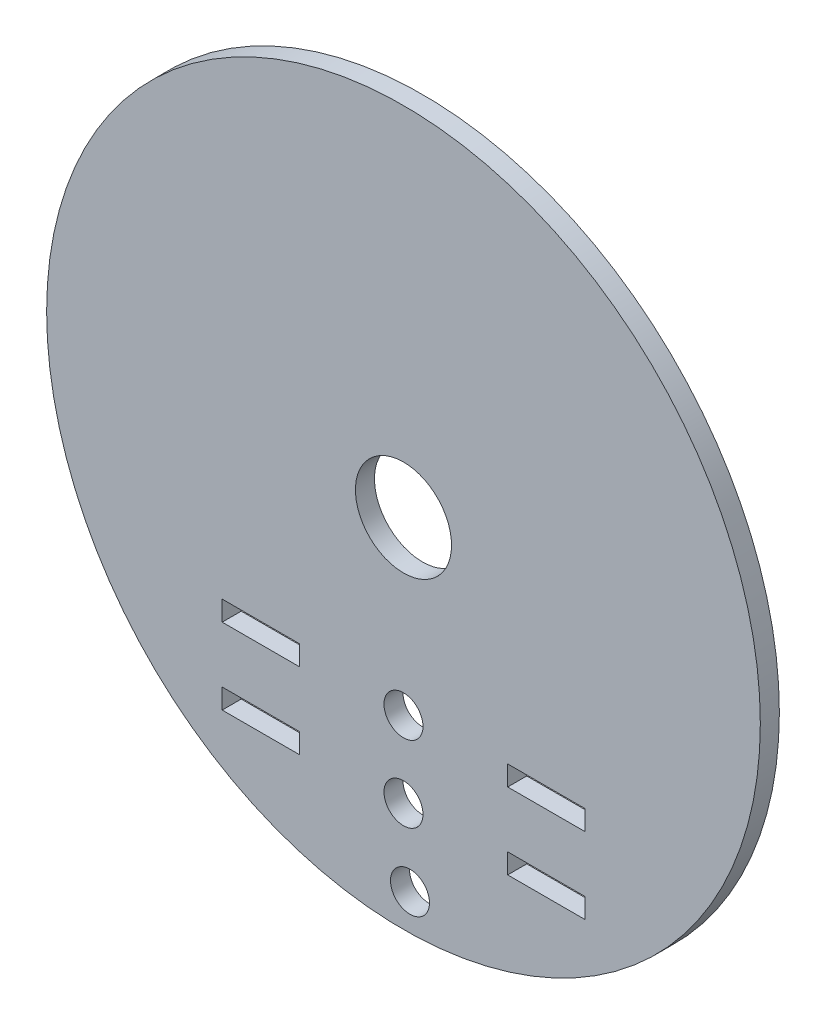
SolidWorks part; units mm, degrees
ref_plane "前视基准面" through (0, 0, 0) normal (0, 0, 1) x (1, 0, 0)
ref_plane "上视基准面" through (0, 0, 0) normal (0, 1, 0) x (1, 0, 0)
ref_plane "右视基准面" through (0, 0, 0) normal (1, 0, 0) x (0, 0, -1)
sketch "草图1" plane through (0, 0, 0) normal (0, 0, 1) x (1, 0, 0)
  line L0 (0, 0) -> (0, 8) construction
  line L1 (0, 8) -> (-15, 8) construction
  line L2 (0, 4) -> (-3.9018, 4) construction
  line L3 (-19.05, 9.05) -> (-10.95, 9.05)
  line L4 (-19.05, 9.05) -> (-19.05, 6.95)
  line L5 (-19.05, 6.95) -> (-10.95, 6.95)
  line L6 (-10.95, 9.05) -> (-10.95, 6.95)
  line L7 (-19.05, 9.05) -> (-10.95, 6.95) construction
  line L8 (-19.05, 6.95) -> (-10.95, 9.05) construction
  line L9 (-10.95, -1.05) -> (-10.95, 1.05)
  line L10 (-19.05, -1.05) -> (-10.95, -1.05)
  line L11 (-19.05, -1.05) -> (-19.05, 1.05)
  line L12 (-19.05, 1.05) -> (-10.95, 1.05)
  line L13 (10.95, 9.05) -> (10.95, 6.95)
  line L14 (19.05, 9.05) -> (10.95, 9.05)
  line L15 (19.05, 9.05) -> (19.05, 6.95)
  line L16 (19.05, 6.95) -> (10.95, 6.95)
  line L17 (19.05, 1.05) -> (10.95, 1.05)
  line L18 (19.05, -1.05) -> (19.05, 1.05)
  line L19 (19.05, -1.05) -> (10.95, -1.05)
  line L20 (10.95, -1.05) -> (10.95, 1.05)
  circle A0 centre (0, 0) radius 2.05
  circle A1 centre (0, 8) radius 2.05
  circle A2 centre (0, 26) radius 5.05
  circle A4 centre (0, 26) radius 12 construction
  circle A6 centre (0, 26) radius 37.5
  circle A7 centre (0.6835, -7.7148) radius 2.05
  dimension "D1" = 4.1
  dimension "D3" = 4.1
  dimension "D7" = 10.1
  dimension "D9" = 24
  dimension "D10" = 75
  dimension "D2" = 8
  dimension "D4" = 15
  dimension "D5" = 8.1
  dimension "D6" = 2.1
  dimension "D8" = 18
extrude "凸台-拉伸1" add sketch "草图1" along normal blind 2
